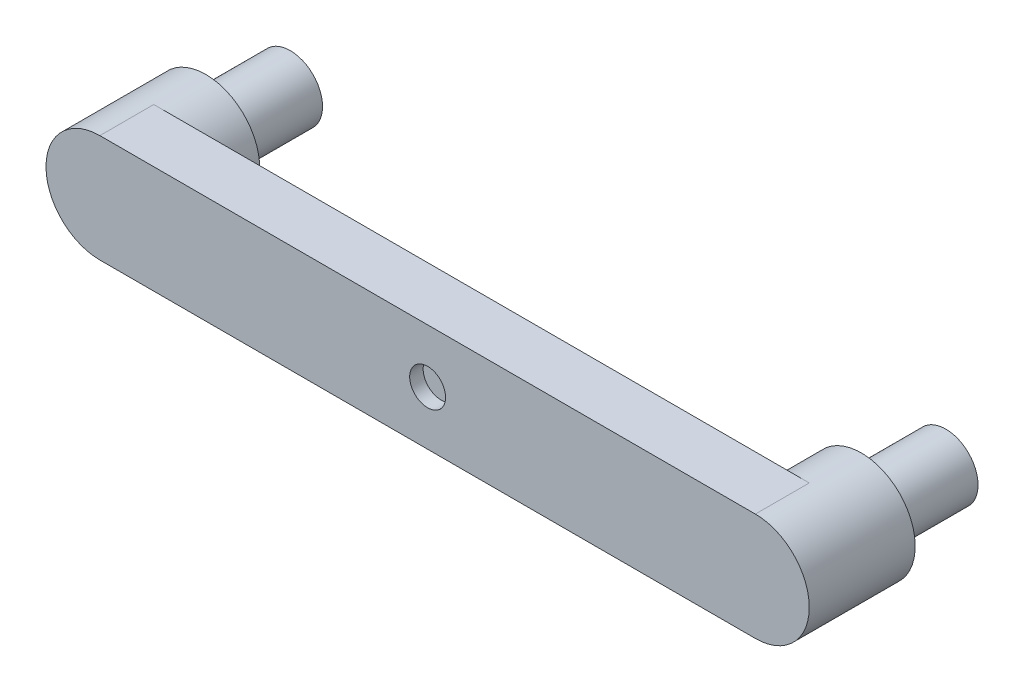
SolidWorks part; units mm, degrees
ref_plane "Front Plane" through (0, 0, 0) normal (0, 0, 1) x (1, 0, 0)
ref_plane "Top Plane" through (0, 0, 0) normal (0, 1, 0) x (1, 0, 0)
ref_plane "Right Plane" through (0, 0, 0) normal (1, 0, 0) x (0, 0, -1)
sketch "Sketch1" plane through (0, 0, 0) normal (0, 0, 1) x (1, 0, 0)
  line L0 (-182.5, 0) -> (182.5, 0) construction
  line L1 (-182.5, 30) -> (182.5, 30)
  line L2 (-182.5, -30) -> (182.5, -30)
  arc A0 (-182.5, 30) -> (-182.5, -30) centre (-182.5, 0) ccw
  arc A1 (182.5, -30) -> (182.5, 30) centre (182.5, 0) ccw
  circle A2 centre (0, 0) radius 10
  circle A3 centre (182.5, 0) radius 18
  circle A4 centre (-182.5, 0) radius 18
  point P2 (0, 0)
  dimension "D1" = 20
  dimension "D2" = 36
  dimension "D3" = 30
  dimension "D4" = 365
extrude "Boss-Extrude1" add sketch "Sketch1" against normal blind 30 contours A4 | L2 A1 L1 A0 A4 A2 A3 | A2 L0 | L0 A2 | A3 region at (182.5, 17.4909, 0) region at (0, 4.2441, 0) region at (0, -4.2441, 0) region at (-199.9909, 0, 0) region at (0, 25.7079, 0)
sketch "Sketch2" plane through (0, 0, -30) normal (0, 0, -1) x (-1, 0, 0)
  circle A1 centre (-182.5, 0) radius 30
  circle A2 centre (182.5, 0) radius 30
  arc A3 (-182.5, 30) -> (-182.5, -30) centre (-182.5, 0) ccw construction
  arc A4 (182.5, -30) -> (182.5, 30) centre (182.5, 0) ccw construction
extrude "Boss-Extrude2" add sketch "Sketch2" along normal blind 29
extrude "Cut-Extrude1" cut sketch "Sketch1<3>" against normal up to surface (30 mm away) contours A2 L0 | L0 A2 region at (0, 4.2441, 0) region at (0, -4.2441, 0) up to face at (0, 0, -30)
sketch "Sketch1<3>" plane through (0, 0, 0) normal (0, 0, 1) x (1, 0, 0) same geometry as "Sketch1"
extrude "Boss-Extrude3" add sketch "Sketch1<4>" against normal blind 47 from surface contours A3 | A4 region at (182.5, 0, 0) region at (-182.5, 0, 0) starting at face at (152.5, 0, -59)
sketch "Sketch1<4>" plane through (0, 0, 0) normal (0, 0, 1) x (1, 0, 0) same geometry as "Sketch1"
sketch "Sketch3" plane through (0, -30, 0) normal (0, -1, 0) x (1, 0, 0)
  line L0 (182.5, -30) -> (182.5, 0) construction
  line L1 (-30, -22.5) -> (30, -22.5)
  line L2 (-30, -22.5) -> (-30, -7.5)
  line L3 (-30, -7.5) -> (30, -7.5)
  line L4 (30, -22.5) -> (30, -7.5)
  point P4 (0, -7.5)
  point P8 (182.5, -15)
  point P9 (30, -15)
  dimension "D1" = 15
  dimension "D2" = 60
extrude "Cut-Extrude2" cut sketch "Sketch3" against normal blind 45
